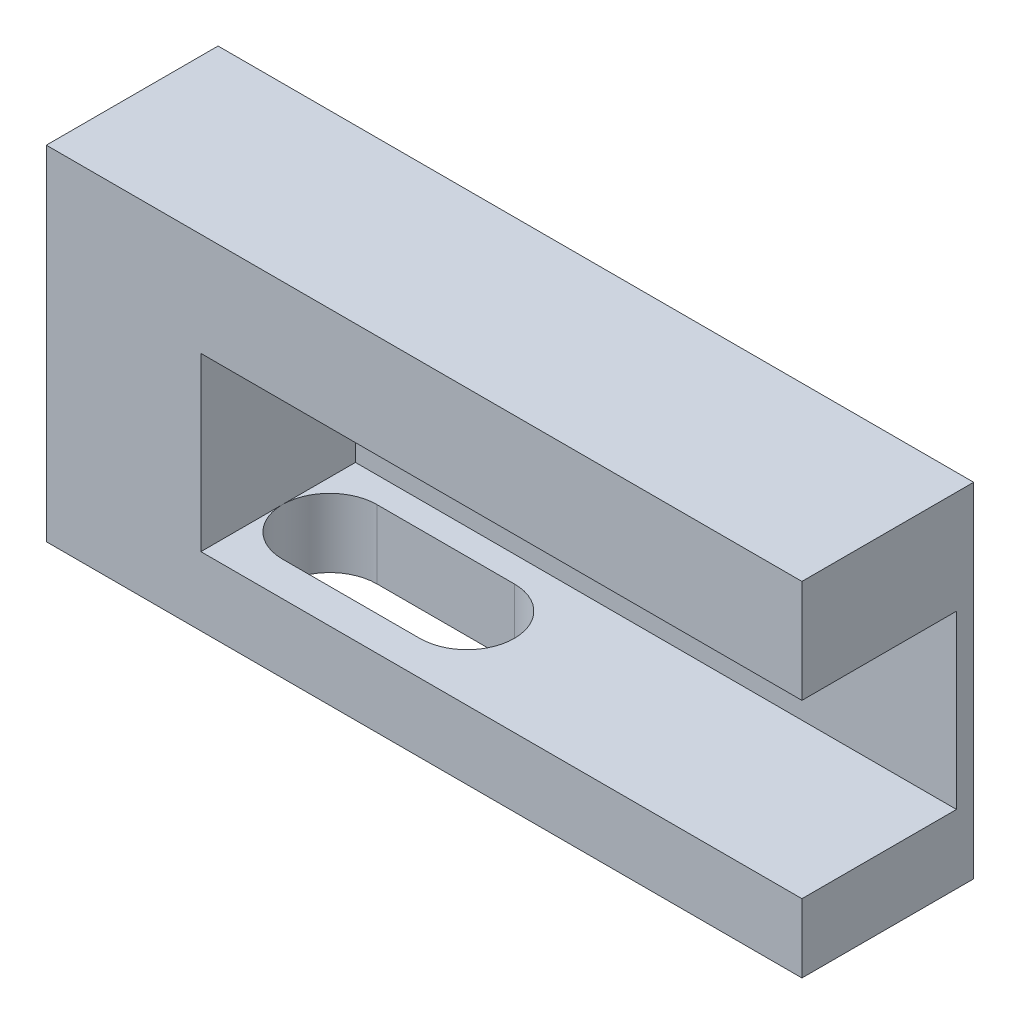
SolidWorks part; units mm, degrees
ref_plane "Plano frontal" through (0, 0, 0) normal (0, 0, 1) x (1, 0, 0)
ref_plane "Plano superior" through (0, 0, 0) normal (0, 1, 0) x (1, 0, 0)
ref_plane "Plano direito" through (0, 0, 0) normal (1, 0, 0) x (0, 0, -1)
sketch "Esboço1" plane through (0, 0, 0) normal (0, 0, 1) x (1, 0, 0)
  line L0 (0, 0) -> (0, 70)
  line L1 (0, 70) -> (20, 70)
  line L2 (20, 70) -> (20, 20)
  line L3 (20, 20) -> (44, 20)
  line L4 (44, 20) -> (44, 0)
  line L5 (44, 0) -> (0, 0)
  dimension "D1" = 24
  dimension "D2" = 20
  dimension "D3" = 70
  dimension "D4" = 20
extrude "Ressalto-extrusão1" add sketch "Esboço1" along normal blind 5
sketch "Esboço5" plane through (0, 0, 5) normal (0, 0, 1) x (1, 0, 0)
  line L0 (0, 0) -> (44, 0) construction
  line L1 (9, 14) -> (44, 14)
  line L2 (9, 14) -> (9, 4)
  line L3 (9, 4) -> (44, 4)
  line L4 (44, 14) -> (44, 4)
  line L6 (44, 0) -> (44, 20) construction
  dimension "D1" = 35
  dimension "D2" = 4
  dimension "D3" = 10
extrude "Corte-extrusão1" cut sketch "Esboço5" against normal blind 4 and the other way through all contours L2 L3 L4 L1
sketch "Esboço6" plane through (0, 0, 5) normal (0, 0, 1) x (1, 0, 0)
  line L0 (44, 20) -> (0, 20)
  line L2 (0, 20) -> (0, 0)
  line L3 (0, 0) -> (44, 0)
  line L4 (44, 0) -> (44, 4)
  line L5 (44, 4) -> (9, 4)
  line L6 (9, 4) -> (9, 14)
  line L7 (9, 14) -> (44, 14)
  line L8 (44, 14) -> (44, 20)
extrude "Ressalto-extrusão2" add sketch "Esboço6" along normal blind 5
fillet "Filete1" radius 5 1 edges at (10, 20, 5)
sketch "Esboço7" plane through (0, 0, 5) normal (0, 0, 1) x (1, 0, 0)
  line L0 (10, 65) -> (10, 55) construction
  line L1 (12.75, 65) -> (12.75, 55)
  line L2 (7.25, 65) -> (7.25, 55)
  line L3 (20, 70) -> (0, 70) construction
  line L4 (0, 70) -> (0, 25) construction
  arc A0 (12.75, 65) -> (7.25, 65) centre (10, 65) ccw
  arc A1 (7.25, 55) -> (12.75, 55) centre (10, 55) ccw
  point P2 (10, 60)
  dimension "D1" = 5
  dimension "D2" = 5.5
  dimension "D3" = 10
  dimension "D4" = 10
extrude "Corte-extrusão2" cut sketch "Esboço7" against normal through all
sketch "Esboço8" plane through (0, 0, 0) normal (0, -1, 0) x (1, 0, 0)
  line L0 (11.75, 5.25) -> (19.75, 5.25) construction
  line L1 (11.75, 8) -> (19.75, 8)
  line L2 (11.75, 2.5) -> (19.75, 2.5)
  line L3 (9, 10) -> (9, 0) construction
  line L4 (0, 10) -> (44, 10) construction
  line L5 (0, 0) -> (44, 0) construction
  line L6 (0, 10) -> (0, 0) construction
  arc A0 (11.75, 8) -> (11.75, 2.5) centre (11.75, 5.25) ccw
  arc A1 (19.75, 2.5) -> (19.75, 8) centre (19.75, 5.25) ccw
  point P2 (15.75, 5.25)
  dimension "D1" = 9
  dimension "D2" = 5.5
  dimension "D3" = 2
  dimension "D4" = 8
extrude "Corte-extrusão3" cut sketch "Esboço8" against normal blind 5
fillet "Filete2" radius 2 2 edges at (0, 70, 2.5) (20, 70, 2.5)
sketch "Esboço10" plane through (0, 0, 10) normal (0, 0, 1) x (1, 0, 0)
  line L1 (20, 20) -> (0, 20)
  line L2 (20, 20) -> (20, 70)
  line L3 (20, 70) -> (0, 70)
  line L4 (0, 20) -> (0, 70)
extrude "Corte-extrusão4" cut sketch "Esboço10" against normal through all
